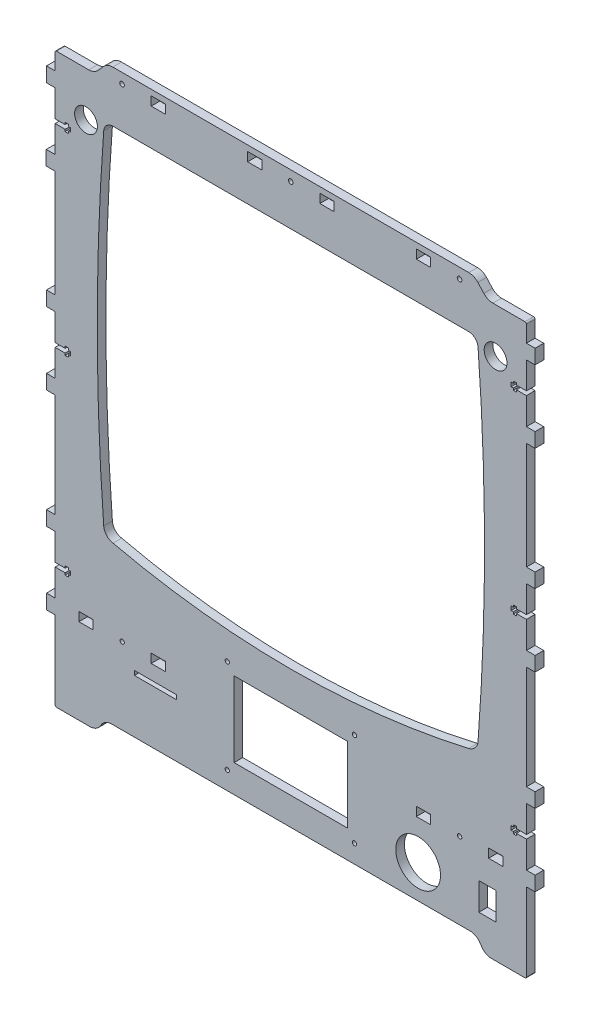
SolidWorks part; units mm, degrees
ref_plane "Спереди" through (0, 0, 0) normal (0, 0, 1) x (1, 0, 0)
ref_plane "Сверху" through (0, 0, 0) normal (0, 1, 0) x (1, 0, 0)
ref_plane "Справа" through (0, 0, 0) normal (1, 0, 0) x (0, 0, -1)
sketch "Эскиз1" plane through (0, 0, 0) normal (0, 0, 1) x (1, 0, 0)
  line L0 (-95.8843, 197.3491) -> (-86.0351, 197.3491)
  line L1 (-86.0351, 197.3491) -> (-86.0351, 191.1493)
  line L2 (-86.0351, 191.1493) -> (-95.8843, 191.1493)
  line L3 (-95.8843, 191.1493) -> (-95.8843, 197.3491)
  line L4 (97.5116, 191.1493) -> (87.6624, 191.1493)
  line L5 (87.6624, 191.1493) -> (87.6624, 197.3491)
  line L6 (87.6624, 197.3491) -> (97.5116, 197.3491)
  line L7 (97.5116, 197.3491) -> (97.5116, 191.1493)
  line L8 (97.5206, -142.9271) -> (87.6714, -142.9271)
  line L9 (87.6714, -142.9271) -> (87.6714, -136.7273)
  line L10 (87.6714, -136.7273) -> (97.5206, -136.7273)
  line L11 (97.5206, -136.7273) -> (97.5206, -142.9271)
  line L12 (147.5206, -142.9271) -> (137.6715, -142.9271)
  line L13 (137.6715, -142.9271) -> (137.6715, -136.7273)
  line L14 (137.6715, -136.7273) -> (147.5206, -136.7273)
  line L15 (147.5206, -136.7273) -> (147.5206, -142.9271)
  line L16 (-136.0441, -142.9271) -> (-145.8933, -142.9271)
  line L17 (-145.8933, -142.9271) -> (-145.8933, -136.7273)
  line L18 (-145.8933, -136.7273) -> (-136.0441, -136.7273)
  line L19 (-136.0441, -136.7273) -> (-136.0441, -142.9271)
  line L20 (-86.0441, -142.9271) -> (-95.8933, -142.9271)
  line L21 (-95.8933, -142.9271) -> (-95.8933, -136.7273)
  line L22 (-95.8933, -136.7273) -> (-86.0441, -136.7273)
  line L23 (-86.0441, -136.7273) -> (-86.0441, -142.9271)
  line L24 (-19.2617, 191.1493) -> (-29.111, 191.1493)
  line L25 (-29.111, 191.1493) -> (-29.111, 197.3491)
  line L26 (-29.111, 197.3491) -> (-19.2617, 197.3491)
  line L27 (-19.2617, 197.3491) -> (-19.2617, 191.1493)
  line L28 (30.7383, 191.1493) -> (20.8891, 191.1493)
  line L29 (20.8891, 191.1493) -> (20.8891, 197.3491)
  line L30 (20.8891, 197.3491) -> (30.7383, 197.3491)
  line L31 (30.7383, 197.3491) -> (30.7383, 191.1493)
  line L32 (-122.1926, 165.873) -> (123.8306, 165.873)
  line L33 (40.0958, -173.6757) -> (40.0958, -121.6757)
  line L34 (40.0958, -121.6757) -> (-38.5042, -121.6757)
  line L35 (-38.5042, -121.6757) -> (-38.5042, -173.6757)
  line L36 (-38.5042, -173.6757) -> (40.0958, -173.6757)
  line L37 (142.9388, -159.6762) -> (142.9388, -178.6762)
  line L38 (142.9388, -178.6762) -> (130.9388, -178.6762)
  line L39 (130.9388, -178.6762) -> (130.9388, -159.6762)
  line L40 (130.9388, -159.6762) -> (142.9388, -159.6762)
  line L41 (-162.3492, -147.0704) -> (-168.3492, -147.0704)
  line L42 (-168.3492, -147.0704) -> (-168.3492, -136.9772)
  line L43 (-168.3492, -136.9772) -> (-162.3492, -136.9772)
  line L44 (-162.3492, -136.9772) -> (-162.3492, -118.3694)
  line L45 (-162.3492, -96.9875) -> (-168.3492, -96.9875)
  line L46 (-168.3492, -96.9875) -> (-168.3492, -86.9875)
  line L47 (-168.3492, -86.9875) -> (-162.3492, -86.9875)
  line L48 (-162.3492, -86.9875) -> (-162.3492, -15.2573)
  line L49 (-162.3492, -15.2573) -> (-168.3492, -15.2573)
  line L50 (-162.3492, 34.7447) -> (-168.3492, 34.7447)
  line L51 (-168.3492, -5.2845) -> (-162.3492, -5.2845)
  line L52 (-168.3492, 44.7175) -> (-162.3492, 44.7175)
  line L53 (-162.3492, 118.8814) -> (-168.5253, 118.8814)
  line L54 (-168.5253, 118.8814) -> (-168.5253, 128.8814)
  line L55 (-168.5253, 128.8814) -> (-162.3492, 128.8814)
  line L56 (-162.3492, 128.8814) -> (-162.3492, 147.4855)
  line L57 (-162.3492, 168.891) -> (-168.3492, 168.891)
  line L58 (-168.3492, 168.891) -> (-168.3492, 179.0334)
  line L59 (-168.3492, 179.0334) -> (-162.3492, 179.0334)
  line L60 (-162.3492, 179.0334) -> (-162.3492, 190.2917)
  line L61 (-162.3492, -201.0193) -> (-162.3492, -147.0704)
  line L62 (163.8508, -146.9772) -> (169.8508, -146.9772)
  line L63 (169.8508, -146.9772) -> (169.8508, -136.9772)
  line L64 (169.8508, -136.9772) -> (163.8508, -136.9772)
  line L65 (163.8508, -136.9772) -> (163.8508, -118.3704)
  line L66 (163.9388, -96.9875) -> (169.8508, -96.9875)
  line L67 (169.8508, -96.9875) -> (169.8508, -86.9875)
  line L68 (169.8508, -86.9875) -> (163.8508, -86.9875)
  line L69 (163.8508, -86.9875) -> (163.8508, -15.2573)
  line L70 (163.8508, -15.2573) -> (169.8508, -15.2573)
  line L71 (163.8508, 34.7447) -> (169.8508, 34.7447)
  line L72 (169.8508, -5.2845) -> (163.8508, -5.2845)
  line L73 (169.8508, 44.7175) -> (163.8508, 44.7175)
  line L74 (163.8508, 118.8814) -> (169.8508, 118.8814)
  line L75 (169.8508, 118.8814) -> (169.8508, 128.8814)
  line L76 (169.8508, 128.8814) -> (163.8508, 128.8814)
  line L77 (163.8508, 128.8814) -> (163.8508, 147.4855)
  line L78 (163.8508, 168.891) -> (169.8508, 168.891)
  line L79 (169.8508, 168.891) -> (169.8508, 178.891)
  line L80 (169.8508, 178.891) -> (163.8508, 178.891)
  line L81 (163.8508, 178.891) -> (163.8508, 190.2917)
  line L82 (156.9388, 150.2865) -> (156.9388, 151.6866)
  line L83 (163.9388, -115.5693) -> (156.9388, -115.5693)
  line L84 (156.9388, -114.1692) -> (154.7379, -114.1692)
  line L85 (156.9413, -118.3692) -> (163.8508, -118.3704)
  line L86 (153.2404, -118.3691) -> (154.7404, -118.3682)
  line L87 (-155.4373, 11.9186) -> (-153.2365, 11.9186)
  line L88 (154.7379, -114.1692) -> (154.7388, -115.5691)
  line L89 (154.7388, 16.1465) -> (153.2388, 16.1457)
  line L90 (153.2388, -115.57) -> (153.2404, -118.3691)
  line L91 (-155.4373, -119.7695) -> (-153.2365, -119.7695)
  line L92 (163.8508, 150.2865) -> (156.9388, 150.2865)
  line L93 (156.9412, -119.7692) -> (156.9413, -118.3692)
  line L94 (156.9388, -115.5693) -> (156.9388, -114.1692)
  line L95 (154.7388, -115.5691) -> (153.2388, -115.57)
  line L96 (154.7404, 147.4877) -> (154.7412, 146.0867)
  line L97 (-155.4398, -114.1696) -> (-155.4398, -115.5696)
  line L98 (154.7404, 13.3475) -> (154.7412, 11.9465)
  line L99 (-162.3492, 147.4855) -> (-155.4373, 147.4855)
  line L100 (-155.4373, 147.4855) -> (-155.4373, 146.0854)
  line L101 (-155.4398, 150.2853) -> (-162.3492, 150.2865)
  line L102 (-153.2389, 150.2844) -> (-153.2398, 151.6853)
  line L103 (154.7404, -118.3682) -> (154.7412, -119.7691)
  line L104 (-155.4398, -115.5696) -> (-162.3492, -115.5684)
  line L105 (154.7379, 151.6866) -> (154.7388, 150.2867)
  line L106 (156.9412, 146.0867) -> (156.9413, 147.4867)
  line L107 (-153.2373, 13.3185) -> (-151.7373, 13.3193)
  line L108 (-155.4373, -118.3694) -> (-155.4373, -119.7695)
  line L109 (153.2388, 150.2859) -> (153.2404, 147.4868)
  line L110 (-153.2398, 17.5457) -> (-155.4398, 17.5457)
  line L111 (-162.3492, 13.3187) -> (-155.4373, 13.3187)
  line L112 (154.7412, 146.0867) -> (156.9412, 146.0867)
  line L113 (153.2404, 147.4868) -> (154.7404, 147.4877)
  line L114 (-153.2373, 147.4853) -> (-151.7373, 147.4862)
  line L115 (-151.7373, 13.3193) -> (-151.7389, 16.1456)
  line L116 (163.8508, 16.1463) -> (156.9388, 16.1463)
  line L117 (154.7379, 17.5193) -> (154.7388, 16.1465)
  line L118 (154.7388, 150.2867) -> (153.2388, 150.2859)
  line L119 (154.7412, 11.9465) -> (156.9412, 11.9465)
  line L120 (-153.2398, -114.1696) -> (-155.4398, -114.1696)
  line L121 (-151.7373, -118.3688) -> (-151.7389, -115.5697)
  line L122 (-153.2373, -118.3696) -> (-151.7373, -118.3688)
  line L123 (-153.2365, 11.9186) -> (-153.2373, 13.3185)
  line L124 (156.9413, 13.3465) -> (163.8508, 13.3453)
  line L125 (-162.3492, -118.3694) -> (-155.4373, -118.3694)
  line L126 (153.2388, 16.1457) -> (153.2404, 13.3466)
  line L127 (-153.2389, -115.5706) -> (-153.2398, -114.1696)
  line L128 (-151.7389, 16.1456) -> (-153.2389, 16.1447)
  line L129 (-155.4373, 146.0854) -> (-153.2365, 146.0854)
  line L130 (-153.2365, -119.7695) -> (-153.2373, -118.3696)
  line L131 (-155.4398, 151.6853) -> (-155.4398, 150.2853)
  line L132 (-151.7389, -115.5697) -> (-153.2389, -115.5706)
  line L133 (-153.2365, 146.0854) -> (-153.2373, 147.4853)
  line L134 (153.2404, 13.3466) -> (154.7404, 13.3475)
  line L135 (156.9388, 151.6866) -> (154.7379, 151.6866)
  line L136 (-151.7373, 147.4862) -> (-151.7389, 150.2852)
  line L137 (156.9413, 147.4867) -> (163.8508, 147.4855)
  line L138 (-155.4398, 16.1457) -> (-162.3492, 16.1469)
  line L139 (156.9412, 11.9465) -> (156.9413, 13.3465)
  line L140 (-155.4398, 17.5457) -> (-155.4398, 16.1457)
  line L141 (154.7412, -119.7691) -> (156.9412, -119.7692)
  line L142 (-153.2398, 151.6853) -> (-155.4398, 151.6853)
  line L143 (156.9388, 17.5193) -> (154.7379, 17.5193)
  line L144 (-151.7389, 150.2852) -> (-153.2389, 150.2844)
  line L145 (-162.3492, -115.5684) -> (-162.3492, -96.9875)
  line L146 (-162.3492, 150.2865) -> (-162.3492, 168.891)
  line L147 (163.9388, -115.5693) -> (163.9388, -96.9875)
  line L148 (163.8508, 150.2865) -> (163.8508, 168.891)
  line L149 (-139.0924, 191.2917) -> (-161.5253, 191.2917)
  line L150 (-128.7242, 198.5304) -> (-132.8221, 194.053)
  line L151 (123.9554, 201.2917) -> (-122.4539, 201.2917)
  line L152 (130.2257, 198.5304) -> (134.3236, 194.053)
  line L153 (140.5939, 191.2917) -> (162.8508, 191.2917)
  line L154 (-131.8015, -198.983) -> (-129.7448, -195.9634)
  line L155 (162.7628, -202.0193) -> (139.7264, -202.0193)
  line L156 (133.303, -198.983) -> (131.2463, -195.9634)
  line L157 (-161.4373, -202.0193) -> (-138.3129, -202.0193)
  line L158 (-123.2334, -192.9271) -> (124.7349, -192.9271)
  line L159 (163.8508, -201.0193) -> (163.8508, -146.9772)
  line L160 (-162.3492, 13.3187) -> (-162.3492, -5.2845)
  line L161 (-168.3492, -15.2573) -> (-168.3492, -5.2845)
  line L162 (-168.3492, 34.7447) -> (-168.3492, 44.7175)
  line L163 (-162.3492, 44.7175) -> (-162.3492, 118.8814)
  line L164 (163.8508, 13.3453) -> (163.8508, -5.2845)
  line L165 (169.8508, -15.2573) -> (169.8508, -5.2845)
  line L166 (169.8508, 34.7447) -> (169.8508, 44.7175)
  line L167 (163.8508, 44.7175) -> (163.8508, 118.8814)
  line L168 (-155.4373, 13.3187) -> (-155.4373, 11.9186)
  line L169 (-153.2389, 16.1447) -> (-153.2398, 17.5457)
  line L170 (156.9388, 16.1463) -> (156.9388, 17.5193)
  line L171 (-162.3492, 34.7447) -> (-162.3492, 16.1469)
  line L172 (163.8508, 34.7447) -> (163.8508, 16.1463)
  line L173 (-107.5042, -155.9271) -> (-107.5042, -152.9271)
  line L174 (-107.5042, -152.9271) -> (-78.5042, -152.9271)
  line L175 (-78.5042, -152.9271) -> (-78.5042, -155.9271)
  line L176 (-78.5042, -155.9271) -> (-107.5042, -155.9271)
  arc A0 (-122.2646, -84.0153) -> (123.8554, -84.0153) centre (0.7954, 449.8336) ccw
  arc A1 (-128.7276, 159.8968) -> (-128.7407, -76.9742) centre (1428.8347, 41.3753) ccw
  arc A2 (130.3319, -76.9742) -> (130.3653, 159.8968) centre (-1430.2964, 41.6814) ccw
  circle A3 centre (44.7958, -115.4257) radius 1.5
  circle A4 centre (44.7958, -180.4257) radius 1.5
  circle A5 centre (-43.2042, -180.4257) radius 1.5
  circle A6 centre (-43.2042, -115.4257) radius 1.5
  circle A7 centre (88.8942, -169.8279) radius 15.5
  arc A8 (130.3653, 159.8968) -> (123.8306, 165.873) centre (123.8306, 159.3123) ccw
  arc A9 (-122.1926, 165.873) -> (-128.7276, 159.8968) centre (-122.2654, 159.3916) ccw
  arc A10 (-128.7407, -76.9742) -> (-122.2646, -84.0153) centre (-121.0385, -76.3888) ccw
  arc A11 (123.8554, -84.0153) -> (130.3319, -76.9742) centre (121.9542, -75.7674) ccw
  circle A12 centre (0.7108, 194.2417) radius 1.6
  circle A13 centre (-116.0492, 194.2417) radius 1.6
  arc A14 (134.3236, 194.053) -> (140.5939, 191.2917) centre (140.5939, 199.7917) ccw
  arc A15 (-161.5253, 191.2917) -> (-162.3492, 190.2917) centre (-161.4373, 190.3797) ccw
  arc A16 (-139.0924, 191.2917) -> (-132.8221, 194.053) centre (-139.0924, 199.7917) ccw
  arc A17 (-122.4539, 201.2917) -> (-128.7242, 198.5304) centre (-122.4539, 192.7917) ccw
  circle A18 centre (117.5508, 194.2417) radius 1.6
  arc A19 (130.2257, 198.5304) -> (123.9554, 201.2917) centre (123.9554, 192.7917) ccw
  arc A20 (163.8508, 190.2917) -> (162.8508, 191.2917) centre (162.8508, 190.2917) ccw
  arc A21 (-123.2334, -192.9271) -> (-129.7448, -195.9634) centre (-123.2334, -201.4271) ccw
  arc A22 (-138.3129, -202.0193) -> (-131.8015, -198.983) centre (-138.3129, -193.5193) ccw
  arc A23 (131.2463, -195.9634) -> (124.7349, -192.9271) centre (124.7349, -201.4271) ccw
  arc A24 (133.303, -198.983) -> (139.7264, -202.0193) centre (139.7704, -193.6137) ccw
  arc A25 (-162.3492, -201.0193) -> (-161.4373, -202.0193) centre (-161.3933, -201.0634) ccw
  arc A26 (162.7628, -202.0193) -> (163.8508, -201.0193) centre (162.8068, -200.9753) ccw
  circle A27 centre (-140.9992, 160.2917) radius 7.9
  circle A28 centre (142.5008, 160.2917) radius 7.9
  circle A29 centre (-115.9455, -139.8588) radius 1.5
  circle A30 centre (117.6444, -139.8477) radius 1.5
extrude "Бобышка-Вытянуть2" add sketch "Эскиз1" along normal blind 6 contours A5 | A4 | A3 | A13 | A12 | A7 | A6 | L32 A8 A2 A11 A0 A10 A1 A9 | A18 | A30 | A29 | A28 | A27 | L4 L5 L6 L7 | L0 L1 L2 L3 | L20 L21 L22 L23 | L16 L17 L18 L19 | L12 L13 L14 L15 | L8 L9 L10 L11 | L37 L38 L39 L40 | L33 L34 L35 L36 | L28 L29 L30 L31 | L24 L25 L26 L27 | L41 L42 L43 L44 L125 L108 L91 L130 L122 L121 L132 L127 L120 L97 L104 L145 L45 L46 L47 L48 L49 L161 L51 L160 L111 L168 L87 L123 L107 L115 L128 L169 L110 L140 L138 L171 L50 L162 L52 L163 L53 L54 L55 L56 L99 L100 L129 L133 L114 L136 L144 L102 L142 L131 L101 L146 L57 L58 L59 L60 A15 L149 A16 L150 A17 L151 A19 L152 A14 L153 A20 L81 L80 L79 L78 L148 L92 L82 L135 L105 L118 L109 L113 L96 L112 L106 L137 L77 L76 L75 L74 L167 L73 L166 L71 L172 L116 L170 L143 L117 L89 L126 L134 L98 L119 L139 L124 L164 L72 L165 L70 L69 L68 L67 L66 L147 L83 L94 L84 L88 L95 L90 L86 L103 L141 L93 L85 L65 L64 L63 L62 L159 A26 L155 A24 L156 A23 L158 A21 L154 A22 L157 A25 L61 | L173 L174 L175 L176
